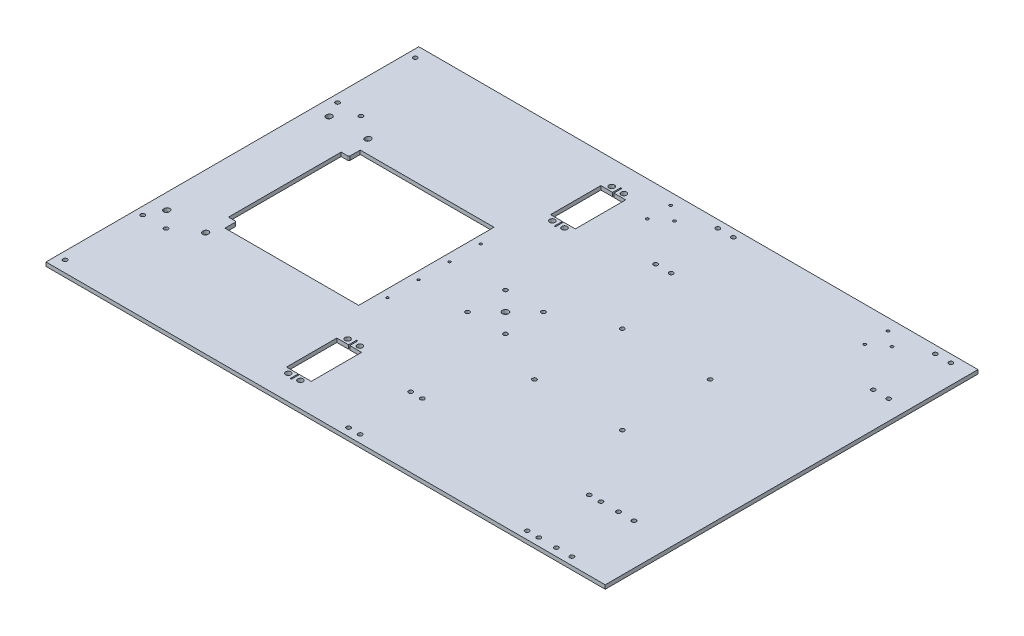
SolidWorks part; units mm, degrees
ref_plane "Front Plane" through (0, 0, 0) normal (0, 0, 1) x (1, 0, 0)
ref_plane "Top Plane" through (0, 0, 0) normal (0, 1, 0) x (1, 0, 0)
ref_plane "Right Plane" through (0, 0, 0) normal (1, 0, 0) x (0, 0, -1)
sketch "Sketch1" plane through (0, 0, 0) normal (0, 1, 0) x (1, 0, 0)
  line L1 (-228.6, -152.4) -> (228.6, -152.4)
  line L2 (-228.6, -152.4) -> (-228.6, 152.4)
  line L3 (-228.6, 152.4) -> (228.6, 152.4)
  line L4 (228.6, -152.4) -> (228.6, 152.4)
  line L5 (-228.6, -152.4) -> (228.6, 152.4) construction
  line L6 (-228.6, 152.4) -> (228.6, -152.4) construction
  point P0 (0, 0)
  dimension "D1" = 304.8
  dimension "D2" = 457.2
extrude "Boss-Extrude1" add sketch "Sketch1" along normal blind 3.175 contours L3 L4 L1 L2
sketch "Sketch2" plane through (0, 3.175, 0) normal (0, 1, 0) x (1, 0, 0)
  line L0 (-215.9, 66.04) -> (-215.9, 66.675) construction
  line L1 (-218.1, 66.04) -> (-218.1, 66.675)
  line L2 (-213.7, 66.04) -> (-213.7, 66.675)
  line L3 (-184.15, 66.04) -> (-184.15, 66.675) construction
  line L4 (-186.35, 66.04) -> (-186.35, 66.675)
  line L5 (-181.95, 66.04) -> (-181.95, 66.675)
  line L6 (-215.9, -66.04) -> (-215.9, -66.675) construction
  line L7 (-213.7, -66.04) -> (-213.7, -66.675)
  line L8 (-218.1, -66.04) -> (-218.1, -66.675)
  line L9 (-184.15, -66.04) -> (-184.15, -66.675) construction
  line L10 (-181.95, -66.04) -> (-181.95, -66.675)
  line L11 (-186.35, -66.04) -> (-186.35, -66.675)
  circle A0 centre (-184.15, -66.675) radius 2.2 construction
  circle A1 centre (-215.9, -66.675) radius 2.2 construction
  circle A2 centre (-184.15, 66.675) radius 2.2 construction
  circle A3 centre (-215.9, 66.675) radius 2.2 construction
  circle A6 centre (-184.15, -66.675) radius 2.2 construction
  circle A7 centre (-215.9, -66.675) radius 2.2 construction
  circle A8 centre (-184.15, 66.675) radius 2.2 construction
  circle A9 centre (-215.9, 66.675) radius 2.2 construction
  arc A10 (-218.1, 66.04) -> (-213.7, 66.04) centre (-215.9, 66.04) ccw
  arc A11 (-213.7, 66.675) -> (-218.1, 66.675) centre (-215.9, 66.675) ccw
  arc A12 (-186.35, 66.04) -> (-181.95, 66.04) centre (-184.15, 66.04) ccw
  arc A13 (-181.95, 66.675) -> (-186.35, 66.675) centre (-184.15, 66.675) ccw
  arc A14 (-213.7, -66.04) -> (-218.1, -66.04) centre (-215.9, -66.04) ccw
  arc A15 (-218.1, -66.675) -> (-213.7, -66.675) centre (-215.9, -66.675) ccw
  arc A16 (-181.95, -66.04) -> (-186.35, -66.04) centre (-184.15, -66.04) ccw
  arc A17 (-186.35, -66.675) -> (-181.95, -66.675) centre (-184.15, -66.675) ccw
  point P9 (-215.9, 66.3575)
  point P19 (-184.15, 66.3575)
  point P25 (-215.9, -66.3575)
  point P30 (-184.15, -66.3575)
  dimension "D1" = 0.635
extrude "Cut-Extrude1" cut sketch "Sketch2" against normal through all
sketch "Sketch3" plane through (0, 3.175, 0) normal (0, 1, 0) x (1, 0, 0)
  line L0 (-228.6, 0) -> (228.6, 0) construction
  line L1 (-228.6, -152.4) -> (-228.6, 152.4) construction
  line L2 (228.6, -152.4) -> (228.6, 152.4) construction
sketch "Sketch4" plane through (0, 3.175, 0) normal (0, 1, 0) x (1, 0, 0)
  line L0 (-185.7375, 46.0375) -> (-185.7375, -46.0375)
  line L1 (-185.7375, -46.0375) -> (-180.34, -46.0375)
  line L2 (-179.3875, -46.99) -> (-179.3875, -55.3085)
  line L3 (-179.3875, -55.3085) -> (-70.0405, -55.3085)
  line L4 (-70.0405, -55.3085) -> (-70.0405, 55.3085)
  line L5 (-70.0405, 55.3085) -> (-179.3875, 55.3085)
  line L6 (-179.3875, 55.3085) -> (-179.3875, 46.99)
  line L7 (-180.34, 46.0375) -> (-185.7375, 46.0375)
  line L8 (-184.15, 44.45) -> (-184.15, -44.45)
  line L9 (-180.34, 44.45) -> (-184.15, 44.45)
  line L10 (-177.8, 53.721) -> (-177.8, 46.99)
  line L11 (-71.628, 53.721) -> (-177.8, 53.721)
  line L12 (-71.628, -53.721) -> (-71.628, 53.721)
  line L13 (-177.8, -53.721) -> (-71.628, -53.721)
  line L14 (-177.8, -46.99) -> (-177.8, -53.721)
  line L15 (-184.15, -44.45) -> (-180.34, -44.45)
  line L16 (-184.15, 44.45) -> (-184.15, -44.45) construction
  line L17 (-180.34, 44.45) -> (-184.15, 44.45) construction
  line L18 (-177.8, 53.721) -> (-177.8, 46.99) construction
  line L19 (-71.628, 53.721) -> (-177.8, 53.721) construction
  line L20 (-71.628, -53.721) -> (-71.628, 53.721) construction
  line L21 (-177.8, -53.721) -> (-71.628, -53.721) construction
  line L22 (-177.8, -46.99) -> (-177.8, -53.721) construction
  line L23 (-184.15, -44.45) -> (-180.34, -44.45) construction
  arc A0 (-179.3875, -46.99) -> (-180.34, -46.0375) centre (-180.34, -46.99) ccw
  arc A1 (-180.34, 46.0375) -> (-179.3875, 46.99) centre (-180.34, 46.99) ccw
  arc A2 (-180.34, 44.45) -> (-177.8, 46.99) centre (-180.34, 46.99) ccw
  arc A3 (-177.8, -46.99) -> (-180.34, -44.45) centre (-180.34, -46.99) ccw
  arc A4 (-180.34, 44.45) -> (-177.8, 46.99) centre (-180.34, 46.99) ccw construction
  arc A5 (-177.8, -46.99) -> (-180.34, -44.45) centre (-180.34, -46.99) ccw construction
  dimension "D2" = 1.5875
extrude "Cut-Extrude2" cut sketch "Sketch4" against normal up to next
sketch "Sketch5" plane through (0, 3.175, 0) normal (0, 1, 0) x (1, 0, 0)
  circle A0 centre (-203.2, 79.629) radius 1.7 construction
  circle A1 centre (-222.25, 143.129) radius 1.7 construction
  circle A2 centre (-222.25, 79.629) radius 1.7 construction
  circle A3 centre (-203.2, -79.629) radius 1.7 construction
  circle A4 centre (-222.25, -79.629) radius 1.7 construction
  circle A5 centre (-222.25, -143.129) radius 1.7 construction
  circle A6 centre (-203.2, 79.629) radius 1.7
  circle A7 centre (-222.25, 143.129) radius 1.7
  circle A8 centre (-222.25, 79.629) radius 1.7
  circle A9 centre (-203.2, -79.629) radius 1.7
  circle A10 centre (-222.25, -79.629) radius 1.7
  circle A11 centre (-222.25, -143.129) radius 1.7
extrude "Cut-Extrude3" cut sketch "Sketch5" against normal through all
sketch "Sketch7" plane through (0, 3.175, 0) normal (0, 1, 0) x (1, 0, 0)
  line L0 (-55.847, -87.373) -> (-35.593, -128.527) construction
  line L1 (-55.847, -87.373) -> (-46.22, -87.373)
  line L2 (-55.847, -87.373) -> (-55.847, -128.527)
  line L3 (-55.847, -128.527) -> (-46.22, -128.527)
  line L4 (-35.593, -87.373) -> (-35.593, -128.527)
  line L5 (-35.593, -87.373) -> (-55.847, -128.527) construction
  line L6 (-50.72, -83.65) -> (-40.72, -132.25) construction
  line L7 (-50.72, -132.25) -> (-40.72, -83.65) construction
  line L9 (-228.6, -152.4) -> (228.6, -152.4) construction
  line L10 (-45.22, -128.527) -> (-35.593, -128.527)
  line L12 (-46.22, -128.527) -> (-46.22, -135.131)
  line L13 (-46.22, -135.131) -> (-45.22, -135.131)
  line L14 (-45.22, -128.527) -> (-45.22, -135.131)
  line L15 (-45.72, -107.95) -> (-2.6371, -107.95) construction
  line L16 (-46.22, -80.769) -> (-45.22, -80.769)
  line L17 (-46.22, -87.373) -> (-46.22, -80.769)
  line L18 (-45.22, -87.373) -> (-45.22, -80.769)
  line L19 (-45.22, -87.373) -> (-35.593, -87.373)
  line L20 (-228.6, -152.4) -> (-228.6, 152.4) construction
  circle A0 centre (-50.72, -132.25) radius 2.2
  circle A1 centre (-40.72, -132.25) radius 2.2
  circle A2 centre (-50.72, -83.65) radius 2.2
  circle A3 centre (-40.72, -83.65) radius 2.2
  point P8 (-45.72, -135.131)
  point P17 (-45.72, -107.95)
  point P18 (-45.72, -107.95)
  dimension "D5" = 4.4
  dimension "D2" = 10
  dimension "D4" = 48.6
  dimension "D1" = 41.154
  dimension "D3" = 20.254
  dimension "D6" = 44.45
  dimension "D7" = 1
  dimension "D8" = 6.604
  dimension "D9" = 182.88
extrude "Cut-Extrude5" cut sketch "Sketch7" against normal through all
mirror "Mirror1" about plane through (0, 0, 0) normal (0, 0, 1) of "Cut-Extrude5"
sketch "Sketch8" plane through (0, 3.175, 0) normal (0, 1, 0) x (1, 0, 0)
  circle A1 centre (-63.6905, -38.1) radius 1
  circle A2 centre (-63.6905, -38.1) radius 1
  circle A3 centre (-63.6905, -12.7) radius 1
  circle A4 centre (-63.6905, -12.7) radius 1
  circle A5 centre (-63.6905, 12.7) radius 1
  circle A6 centre (-63.6905, 12.7) radius 1
  circle A7 centre (-63.6905, 38.1) radius 1
  circle A8 centre (-63.6905, 38.1) radius 1
  dimension "D1" = 0
  dimension "D2" = 0
  dimension "D3" = 0
  dimension "D4" = 0
extrude "Cut-Extrude6" cut sketch "Sketch8" against normal through all
sketch "Sketch12" plane through (0, 3.175, 0) normal (0, 1, 0) x (1, 0, 0)
  circle A0 centre (195.024, -95.25) radius 1.7 construction
  circle A1 centre (182.324, -95.25) radius 1.7 construction
  circle A2 centre (195.024, -146.05) radius 1.7 construction
  circle A3 centre (182.324, -146.05) radius 1.7 construction
  circle A4 centre (167.9575, -95.25) radius 1.7 construction
  circle A5 centre (158.4325, -95.25) radius 1.7 construction
  circle A6 centre (167.9575, -146.05) radius 1.7 construction
  circle A7 centre (158.4325, -146.05) radius 1.7 construction
  circle A8 centre (21.9075, -146.05) radius 1.7 construction
  circle A9 centre (12.3825, -146.05) radius 1.7 construction
  circle A10 centre (12.3825, -95.25) radius 1.7 construction
  circle A11 centre (21.9075, -95.25) radius 1.7 construction
  circle A12 centre (195.024, -95.25) radius 1.7
  circle A13 centre (182.324, -95.25) radius 1.7
  circle A14 centre (195.024, -146.05) radius 1.7
  circle A15 centre (182.324, -146.05) radius 1.7
  circle A16 centre (167.9575, -95.25) radius 1.7
  circle A17 centre (158.4325, -95.25) radius 1.7
  circle A18 centre (167.9575, -146.05) radius 1.7
  circle A19 centre (158.4325, -146.05) radius 1.7
  circle A20 centre (21.9075, -146.05) radius 1.7
  circle A21 centre (12.3825, -146.05) radius 1.7
  circle A22 centre (12.3825, -95.25) radius 1.7
  circle A23 centre (21.9075, -95.25) radius 1.7
extrude "Cut-Extrude7" cut sketch "Sketch12" against normal through all
sketch "Sketch13" plane through (0, 3.175, 0) normal (0, 1, 0) x (1, 0, 0)
  circle A1 centre (212.725, 95.25) radius 1.7
  circle A2 centre (212.725, 95.25) radius 1.7
  circle A3 centre (212.725, 146.05) radius 1.7
  circle A4 centre (212.725, 146.05) radius 1.7
  circle A5 centre (200.025, 95.25) radius 1.7
  circle A6 centre (200.025, 95.25) radius 1.7
  circle A7 centre (200.025, 146.05) radius 1.7
  circle A8 centre (200.025, 146.05) radius 1.7
  circle A9 centre (177.213, 133.477) radius 1.127
  circle A10 centre (177.213, 133.477) radius 1.127
  circle A11 centre (164.513, 143.002) radius 1.127
  circle A12 centre (164.513, 143.002) radius 1.127
  circle A13 centre (164.513, 123.952) radius 1.127
  circle A14 centre (164.513, 123.952) radius 1.127
  circle A15 centre (34.925, 95.25) radius 1.7
  circle A16 centre (34.925, 95.25) radius 1.7
  circle A17 centre (34.925, 146.05) radius 1.7
  circle A18 centre (34.925, 146.05) radius 1.7
  circle A19 centre (22.225, 95.25) radius 1.7
  circle A20 centre (22.225, 95.25) radius 1.7
  circle A21 centre (22.225, 146.05) radius 1.7
  circle A22 centre (22.225, 146.05) radius 1.7
  circle A23 centre (-0.587, 133.477) radius 1.127
  circle A24 centre (-0.587, 133.477) radius 1.127
  circle A25 centre (-13.287, 143.002) radius 1.127
  circle A26 centre (-13.287, 143.002) radius 1.127
  circle A27 centre (-13.287, 123.952) radius 1.127
  circle A28 centre (-13.287, 123.952) radius 1.127
  dimension "D1" = 0
  dimension "D2" = 0
  dimension "D3" = 0
  dimension "D4" = 0
  dimension "D5" = 0
  dimension "D6" = 0
  dimension "D7" = 0
  dimension "D8" = 0
  dimension "D9" = 0
  dimension "D10" = 0
  dimension "D11" = 0
  dimension "D12" = 0
  dimension "D13" = 0
  dimension "D14" = 0
extrude "Cut-Extrude8" cut sketch "Sketch13" against normal through all
sketch "Sketch14" plane through (0, 3.175, 0) normal (0, 1, 0) x (1, 0, 0)
  line L0 (-20.834, -15.5) -> (10.166, -15.5) construction
  line L1 (54.249, -35.921) -> (126.091, -35.921) construction
  line L2 (54.249, -35.921) -> (54.249, 35.921) construction
  line L3 (54.249, 35.921) -> (126.091, 35.921) construction
  line L4 (126.091, -35.921) -> (126.091, 35.921) construction
  line L5 (54.249, -35.921) -> (126.091, 35.921) construction
  line L6 (54.249, 35.921) -> (126.091, -35.921) construction
  line L7 (-20.834, -15.5) -> (-20.834, 15.5) construction
  line L8 (-20.834, 15.5) -> (10.166, 15.5) construction
  line L9 (10.166, -15.5) -> (10.166, 15.5) construction
  line L10 (-20.834, -15.5) -> (10.166, 15.5) construction
  line L11 (-20.834, 15.5) -> (10.166, -15.5) construction
  circle A0 centre (90.17, 0) radius 9.525 construction
  circle A1 centre (-5.334, 0) radius 2.6035 construction
  circle A2 centre (90.17, 0) radius 9.525 construction
  circle A3 centre (-5.334, 0) radius 2.6035 construction
  circle A4 centre (54.249, 35.921) radius 1.7
  circle A5 centre (126.091, 35.921) radius 1.7
  circle A7 centre (54.249, -35.921) radius 1.7
  circle A9 centre (126.091, -35.921) radius 1.7
  circle A12 centre (-20.834, 15.5) radius 1.7
  circle A13 centre (10.166, 15.5) radius 1.7
  circle A14 centre (-20.834, -15.5) radius 1.7
  circle A15 centre (10.166, -15.5) radius 1.7
  circle A16 centre (-5.334, 0) radius 2.5
  dimension "D2" = 3.4
  dimension "D5" = 3.4
  dimension "D6" = 5
  dimension "D4" = 31
  dimension "D1" = 101.6
extrude "Cut-Extrude9" cut sketch "Sketch14" against normal through all
equation "\"tightTol\"= 0.005in"
equation "\"normTol\"= 0.01in"
equation "\"looseTol\"= 0.02in"
equation "\"D2@Sketch4\"=1/16"
equation "\"D2@Sketch14\"=3.4mm"
equation "\"D5@Sketch7\"=4.4mm"
